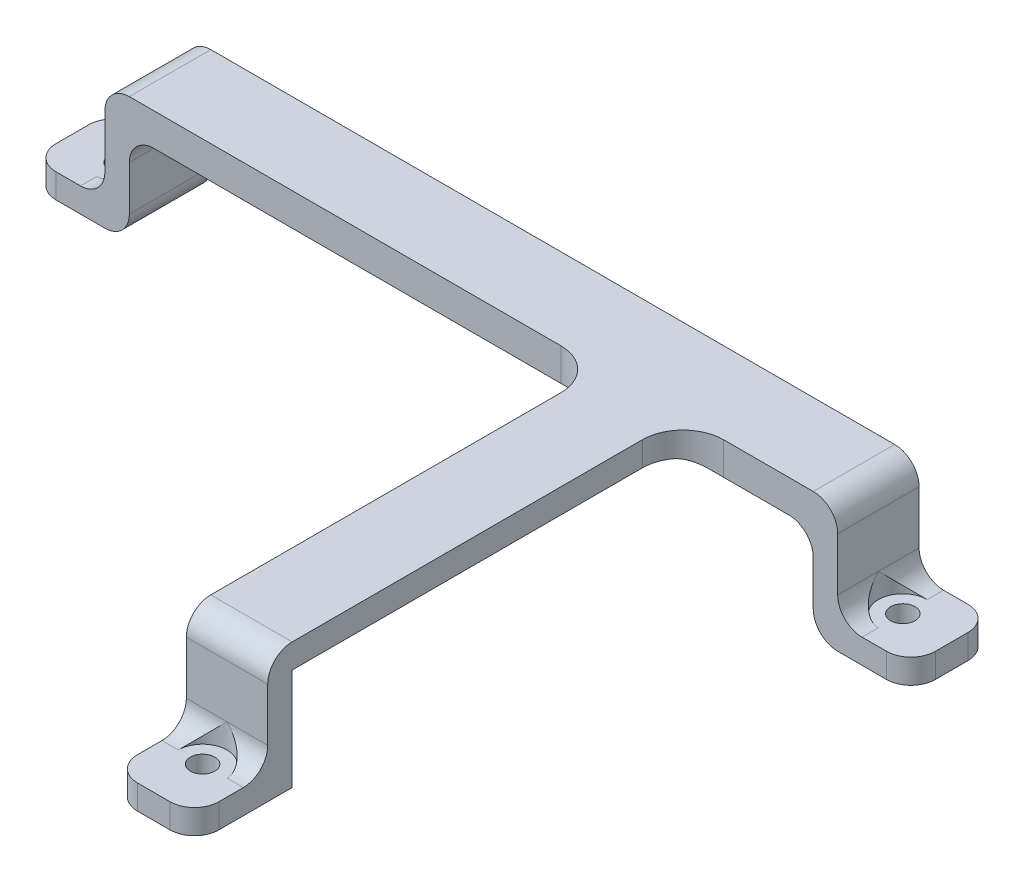
SolidWorks part; units mm, degrees
ref_plane "Front Plane" through (0, 0, 0) normal (0, 0, 1) x (1, 0, 0)
ref_plane "Top Plane" through (0, 0, 0) normal (0, 1, 0) x (1, 0, 0)
ref_plane "Right Plane" through (0, 0, 0) normal (1, 0, 0) x (0, 0, -1)
sketch "Sketch1" plane through (0, 0, 0) normal (0, 1, 0) x (1, 0, 0)
  line L1 (-75, 64) -> (-63, 64)
  line L2 (-75, 64) -> (-75, 54)
  line L3 (-75, 54) -> (-63, 54)
  line L4 (-63, 64) -> (-63, 54)
  line L5 (21, 64) -> (33, 64)
  line L6 (21, 64) -> (21, 54)
  line L7 (21, 54) -> (33, 54)
  line L8 (33, 64) -> (33, 54)
  line L9 (-5, 6) -> (5, 6)
  line L10 (-5, 6) -> (-5, -6)
  line L11 (-5, -6) -> (5, -6)
  line L12 (5, 6) -> (5, -6)
  circle A0 centre (0, 0) radius 1.5
  circle A1 centre (-69, 59) radius 1.5
  circle A2 centre (27, 59) radius 1.5
  point P19 (-75, 59)
  point P21 (33, 59)
  point P22 (0, 6)
  dimension "D1" = 3
  dimension "D3" = 59
  dimension "D2" = 69
  dimension "D4" = 96
  dimension "D5" = 6
  dimension "D6" = 6
  dimension "D7" = 12
  dimension "D8" = 12
  dimension "D9" = 6
  dimension "D10" = 12
  dimension "D11" = 10
  dimension "D12" = 10
  dimension "D13" = 10
extrude "Screw tabs" add sketch "Sketch1" along normal blind 3
sketch "Sketch2" plane through (0, 3, 0) normal (0, 1, 0) x (1, 0, 0)
  line L0 (-75, 54) -> (-63, 54) construction
  line L1 (-63, 64) -> (-66, 64)
  line L2 (-63, 64) -> (-63, 54)
  line L3 (-63, 54) -> (-66, 54)
  line L4 (-66, 64) -> (-66, 54)
  line L5 (5, -6) -> (5, 6) construction
  line L6 (21, 64) -> (24, 64)
  line L7 (21, 64) -> (21, 54)
  line L8 (21, 54) -> (24, 54)
  line L9 (24, 64) -> (24, 54)
  line L10 (-5, 6) -> (5, 6)
  line L11 (-5, 6) -> (-5, 3)
  line L12 (-5, 3) -> (5, 3)
  line L13 (5, 6) -> (5, 3)
  line L14 (21, 54) -> (33, 54) construction
  dimension "D1" = 3
extrude "Vertical extrude" add sketch "Sketch2" along normal blind 9.5
sketch "Sketch3" plane through (0, 12.5, 0) normal (0, 1, 0) x (1, 0, 0)
  line L0 (5, 3) -> (5, 6) construction
  line L1 (-66, 64) -> (24, 64)
  line L2 (-66, 64) -> (-66, 54)
  line L3 (-66, 54) -> (-10, 54)
  line L4 (24, 64) -> (24, 54)
  line L5 (-5, 3) -> (5, 3)
  line L6 (-5, 3) -> (-5, 49)
  line L8 (5, 3) -> (5, 49)
  line L9 (10, 54) -> (24, 54)
  arc A0 (10, 54) -> (5, 49) centre (10, 49) ccw
  arc A1 (-5, 49) -> (-10, 54) centre (-10, 49) ccw
  point P15 (5, 54)
  dimension "D1" = 5
extrude "Top bracket" add sketch "Sketch3" along normal blind 3
sketch "Sketch5" plane through (0, 12.5, 0) normal (0, -1, 0) x (1, 0, 0)
  line L0 (-10, -54) -> (10, -54)
  line L10 (5, -6) -> (-5, -6)
  line L11 (-5, -6) -> (-5, -49)
  line L12 (-10, -54) -> (-63, -54)
  line L15 (-63, -54) -> (-63, -64)
  line L16 (-63, -64) -> (21, -64)
  line L17 (21, -64) -> (21, -54)
  line L18 (21, -54) -> (10, -54)
  line L19 (5, -49) -> (5, -6)
  line L22 (-10, -54) -> (-63, -54)
  line L25 (-63, -54) -> (-63, -64)
  line L26 (-63, -64) -> (21, -64)
  line L27 (21, -64) -> (21, -54)
  line L28 (21, -54) -> (10, -54)
  arc A2 (-10, -54) -> (-5, -49) centre (-10, -49) ccw
  arc A3 (5, -49) -> (10, -54) centre (10, -49) ccw
  dimension "D1" = 0
extrude "Horizontal part thickening (to contact ETH port)" add sketch "Sketch5" along normal blind 1
fillet "3mm edge rounding" radius 3 17 edges at (-63, 0, -59) (21, 0, -59) (24, 3, -59) (0, 3, -3) (-66, 3, -59) (33, 1.5, -64) (33, 1.5, -54) (5, 1.5, 6) (-5, 1.5, 6) (-75, 1.5, -64) (-75, 1.5, -54) (24, 15.5, -59) (0, 15.5, -3) (-66, 15.5, -59) (0, 12.5, -54) (-63, 11.5, -59) (21, 11.5, -59)
sketch "Sketch4" plane through (0, 3, 0) normal (0, 1, 0) x (1, 0, 0)
  circle A8 centre (-69, 59) radius 3
  circle A9 centre (-69, 59) radius 3
  circle A11 centre (0, 0) radius 3
  circle A12 centre (0, 0) radius 3
  circle A14 centre (27, 59) radius 3
  circle A15 centre (27, 59) radius 3
  dimension "D1" = 1.5
  dimension "D2" = 1.5
  dimension "D3" = 1.5
extrude "Screwhole clearup" cut sketch "Sketch4" along normal through all
